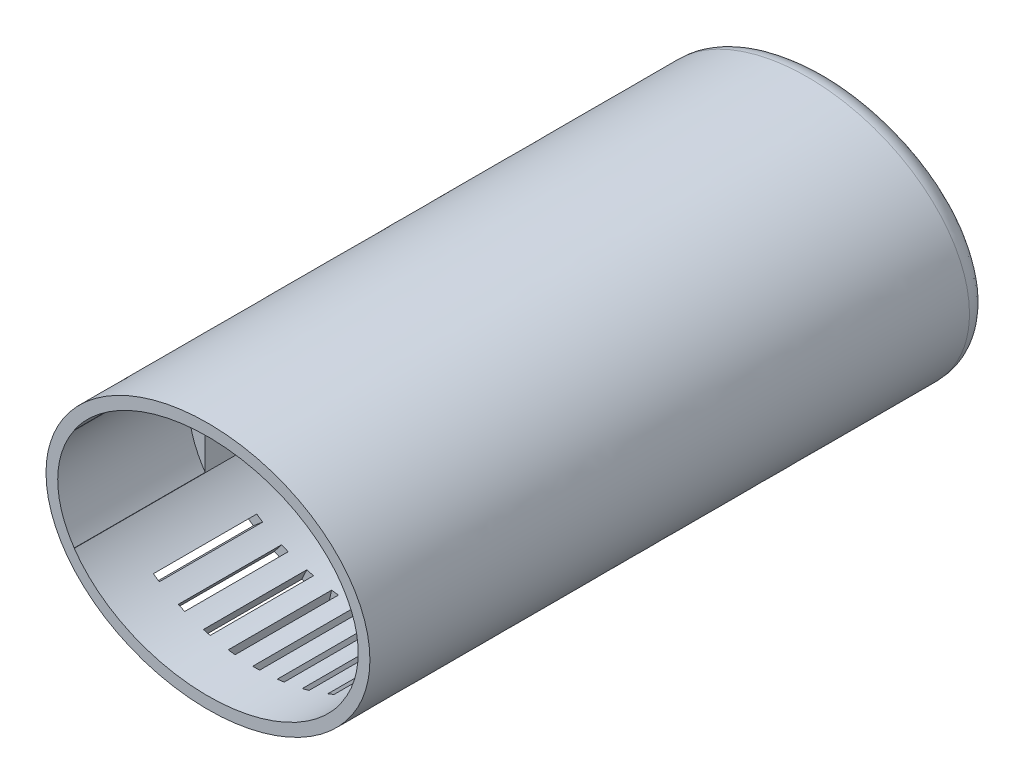
SolidWorks part; units mm, degrees
ref_plane "Ebene vorne" through (0, 0, 0) normal (0, 0, 1) x (1, 0, 0)
ref_plane "Ebene oben" through (0, 0, 0) normal (0, 1, 0) x (1, 0, 0)
ref_plane "Ebene rechts" through (0, 0, 0) normal (1, 0, 0) x (0, 0, -1)
sketch "Skizze1" plane through (0, 0, 0) normal (0, 0, 1) x (1, 0, 0)
  ellipse E0 centre (0, 0) end of major axis (23.5, 0) minor radius 18
  dimension "D1" = 18
  dimension "D2" = 23.5
extrude "Aufsatz-Linear austragen1" add sketch "Skizze1" along normal blind 90
sketch "Skizze2" plane through (0, 0, 90) normal (0, 0, 1) x (1, 0, 0)
  line L2 (-19.4, 7.4351) -> (-19.4, -7.4351)
  line L4 (19.4, 7.4351) -> (19.4, -7.4351)
  line L5 (-13.6079, 12.7344) -> (13.6079, -12.7344) construction
  line L6 (-13.6079, -12.7344) -> (13.6079, 12.7344) construction
  ellipse E0 centre (0, 0) end of major axis (21.8, 0) minor radius 16.3 (-19.4, -7.4351) -> (19.4, -7.4351) ccw
  ellipse E1 centre (0, 0) end of major axis (21.8, 0) minor radius 16.3 (19.4, 7.4351) -> (-19.4, 7.4351) ccw
  dimension "D1" = 16.3
  dimension "D2" = 21.8
extrude "Schnitt-Linear austragen1" cut sketch "Skizze2" against normal blind 88.5
sketch "Skizze3" plane through (0, 0, 1.5) normal (0, 0, 1) x (1, 0, 0)
  line L0 (-24.7423, 0) -> (24.4529, 0) construction
  line L1 (-19.4, 7.4351) -> (-19.4, -7.4351) construction
  line L2 (-19.4, 0.5) -> (-16.4, 0.5)
  line L3 (-19.4, 0.5) -> (-19.4, 3.5)
  line L4 (-19.4, 3.5) -> (-16.4, 3.5)
  line L5 (-16.4, 0.5) -> (-16.4, 3.5)
  line L6 (19.4, -7.4351) -> (19.4, 7.4351) construction
  line L7 (19.4, 3.5) -> (16.4, 3.5)
  line L8 (19.4, 3.5) -> (19.4, 0.5)
  line L9 (19.4, 0.5) -> (16.4, 0.5)
  line L10 (16.4, 3.5) -> (16.4, 0.5)
  dimension "D1" = 3
  dimension "D2" = 3
  dimension "D3" = 3.5
  dimension "D4" = 3
  dimension "D5" = 3
  dimension "D6" = 3.5
extrude "Aufsatz-Linear austragen2" add sketch "Skizze3" along normal blind 60
fillet "Verrundung1" radius 3 1 edges at (23.5, 0, 0)
sketch "Skizze4" plane through (0, 0, 90) normal (0, 0, 1) x (1, 0, 0)
  line L0 (-1.8808, -10.8114) -> (-2.8571, -10.595)
  line L1 (0.5, -10.9629) -> (-0.5, -10.9629)
  line L2 (0.5, -10.9629) -> (0.5, -21.6371)
  line L3 (0.5, -21.6371) -> (-0.5, -21.6371)
  line L4 (-0.5, -10.9629) -> (-0.5, -21.6371)
  line L5 (0.5, -10.9629) -> (-0.5, -21.6371) construction
  line L6 (0.5, -21.6371) -> (-0.5, -10.9629) construction
  line L7 (-1.8808, -10.8114) -> (-4.1912, -21.2327)
  line L8 (-4.1912, -21.2327) -> (-5.1675, -21.0163)
  line L9 (-2.8571, -10.595) -> (-5.1675, -21.0163)
  line L10 (-1.8808, -10.8114) -> (-5.1675, -21.0163) construction
  line L11 (-4.1912, -21.2327) -> (-2.8571, -10.595) construction
  line L12 (-4.1725, -10.1483) -> (-5.0788, -9.7257)
  line L13 (-4.1725, -10.1483) -> (-8.6836, -19.8225)
  line L14 (-8.6836, -19.8225) -> (-9.5899, -19.3999)
  line L15 (-5.0788, -9.7257) -> (-9.5899, -19.3999)
  line L16 (-4.1725, -10.1483) -> (-9.5899, -19.3999) construction
  line L17 (-8.6836, -19.8225) -> (-5.0788, -9.7257) construction
  line L18 (-6.2663, -9.0049) -> (-7.0596, -8.3961)
  line L19 (-6.2663, -9.0049) -> (-12.7644, -17.4734)
  line L20 (-12.7644, -17.4734) -> (-13.5577, -16.8646)
  line L21 (-7.0596, -8.3961) -> (-13.5577, -16.8646)
  line L22 (-6.2663, -9.0049) -> (-13.5577, -16.8646) construction
  line L23 (-12.7644, -17.4734) -> (-7.0596, -8.3961) construction
  line L24 (-8.063, -7.4354) -> (-8.7057, -6.6694)
  line L25 (-8.063, -7.4354) -> (-16.2399, -14.2967)
  line L26 (-16.2399, -14.2967) -> (-16.8827, -13.5307)
  line L27 (-8.7057, -6.6694) -> (-16.8827, -13.5307)
  line L28 (-8.063, -7.4354) -> (-16.8827, -13.5307) construction
  line L29 (-16.2399, -14.2967) -> (-8.7057, -6.6694) construction
  line L30 (2.8609, -10.5948) -> (1.8846, -10.8112)
  line L31 (2.8609, -10.5948) -> (5.1713, -21.016)
  line L32 (5.1713, -21.016) -> (4.195, -21.2325)
  line L33 (1.8846, -10.8112) -> (4.195, -21.2325)
  line L34 (2.8609, -10.5948) -> (4.195, -21.2325) construction
  line L35 (5.1713, -21.016) -> (1.8846, -10.8112) construction
  line L36 (5.0863, -9.7244) -> (4.18, -10.147)
  line L37 (5.0863, -9.7244) -> (9.5974, -19.3986)
  line L38 (9.5974, -19.3986) -> (8.6911, -19.8212)
  line L39 (4.18, -10.147) -> (8.6911, -19.8212)
  line L40 (5.0863, -9.7244) -> (8.6911, -19.8212) construction
  line L41 (9.5974, -19.3986) -> (4.18, -10.147) construction
  line L42 (7.0704, -8.393) -> (6.2771, -9.0018)
  line L43 (7.0704, -8.393) -> (13.5685, -16.8615)
  line L44 (13.5685, -16.8615) -> (12.7752, -17.4703)
  line L45 (6.2771, -9.0018) -> (12.7752, -17.4703)
  line L46 (7.0704, -8.393) -> (12.7752, -17.4703) construction
  line L47 (13.5685, -16.8615) -> (6.2771, -9.0018) construction
  line L48 (8.7194, -6.6638) -> (8.0766, -7.4298)
  line L49 (8.7194, -6.6638) -> (16.8964, -13.5251)
  line L50 (16.8964, -13.5251) -> (16.2536, -14.2911)
  line L51 (8.0766, -7.4298) -> (16.2536, -14.2911)
  line L52 (8.7194, -6.6638) -> (16.2536, -14.2911) construction
  line L53 (16.8964, -13.5251) -> (8.0766, -7.4298) construction
  ellipse E0 centre (0, 0) end of major axis (21.8, 0) minor radius 16.3 (-19.4, -7.4351) -> (19.4, -7.4351) ccw construction
  point P0 (0, -16.3)
  point P15 (-3.5242, -15.9139)
  point P20 (-6.8812, -14.7741)
  point P25 (-9.912, -12.9347)
  point P30 (-12.4728, -10.483)
  point P35 (0.0009, -0.0175)
  point P36 (3.528, -15.9136)
  point P41 (6.8887, -14.7728)
  point P46 (9.9228, -12.9317)
  point P51 (12.4865, -10.4774)
  point P56 (0, 0)
  dimension "D1" = 1
  dimension "D2" = 5
  dimension "D3" = 5
extrude "Schnitt-Linear austragen2" cut sketch "Skizze4" against normal blind 15 from offset 7 offset against normal yes
pattern_linear "Lineares Muster1" count 2 spacing 60 along (0, 0, -1) of "Schnitt-Linear austragen2"
sketch "Skizze5" plane through (0, 0, 90) normal (0, 0, 1) x (1, 0, 0)
  ellipse E0 centre (0, 0) end of major axis (21.8, 0) minor radius 16.2
extrude "Schnitt-Linear austragen3" cut sketch "Skizze5" against normal blind 19
chamfer "Fase1" distance 3 angle 45 2 edges at (-19.4, 2, 61.5) (19.4, 2, 61.5)
fillet "Verrundung2" radius 1 1 edges at (0, -16.3, 1.5)
fillet "Verrundung3" radius 1 1 edges at (0, 16.3, 1.5)
